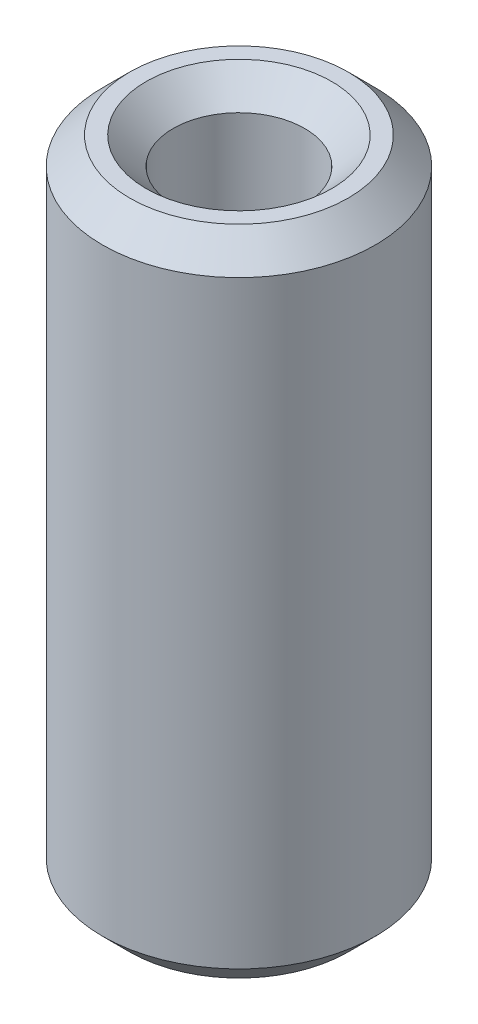
SolidWorks part; units mm, degrees
ref_plane "Front Plane" through (0, 0, 0) normal (0, 0, 1) x (1, 0, 0)
ref_plane "Top Plane" through (0, 0, 0) normal (0, 1, 0) x (1, 0, 0)
ref_plane "Right Plane" through (0, 0, 0) normal (1, 0, 0) x (0, 0, -1)
sketch "Sketch1" plane through (0, 0, 0) normal (0, 1, 0) x (1, 0, 0)
  circle A0 centre (0, 0) radius 10
  dimension "SLEEVE_OD" = 20
extrude "Boss-Extrude1" add sketch "Sketch1" along normal blind 47.893
sketch "Sketch2" plane through (0, 0, 0) normal (0, 1, 0) x (1, 0, 0)
  circle A0 centre (0, 0) radius 4.822
  dimension "BORE_D" = 9.644
extrude "Cut-Extrude1" cut sketch "Sketch2" along normal through all
chamfer "Chamfer1" distance 1.9874 angle 45 4 edges at (0, 47.893, 4.822) (0, 0, 4.822) (0, 0, 10) (0, 47.893, 10)
